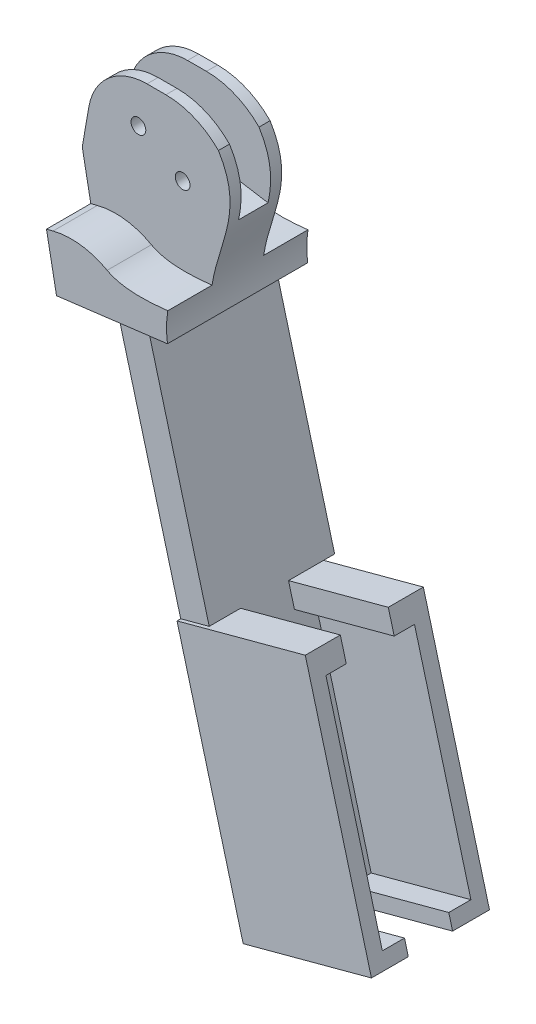
SolidWorks part; units mm, degrees
ref_plane "Спереди" through (0, 0, 0) normal (0, 0, 1) x (1, 0, 0)
ref_plane "Сверху" through (0, 0, 0) normal (0, 1, 0) x (1, 0, 0)
ref_plane "Справа" through (0, 0, 0) normal (1, 0, 0) x (0, 0, -1)
sketch "Sketch5" plane through (0, 0, 0) normal (0, 0, 1) x (1, 0, 0)
  line L0 (1.7523, 0.4742) -> (37.3029, 86.8114) construction
  line L1 (-1.0106, -0.6044) -> (29.6618, 87.5839) construction
  line L2 (0, 0) -> (17.8901, 43.1295)
  line L3 (0, 0) -> (114.3643, 0) construction
  line L4 (23.8823, 39.6684) -> (24.5035, 51.2503)
  line B0 (17.4507, 115.16) -> (29.9551, 112.6983)
  spline B1 degree 3 poles (29.9551, 112.6983) (28.321, 116.0983) (27.9284, 121.1676) (30.1713, 134.4746) (29.8473, 132.0116) (30.6222, 139.9349) (27.0176, 140.9027) knots 0 0 0 0 0.297085 0.369784 0.687298 1 1 1 1
  spline B2 degree 2 poles (27.0176, 140.9027) (20.5603, 128.6427) (17.4507, 115.16) knots 0 0 0 1 1 1
  spline B3 degree 2 poles (27.0176, 140.9027) (26.5004, 134.6878) (22.2537, 130.5645) knots 0 0 0 1 1 1
  line B4 (17.1977, 114.3508) -> (29.842, 112.2111)
  line B5 (28.7001, 84.8969) -> (10.3668, 87.513)
  spline B6 degree 1 poles (17.1977, 114.3508) (10.3668, 87.513) knots 0 0 1 1
  spline B7 degree 2 poles (29.842, 112.2111) (22.5534, 98.8452) (28.7001, 84.8969) knots 0 0 0 1 1 1
  line B8 (10.1904, 87.4159) -> (28.2572, 84.4958)
  line B9 (32.8909, 45.7292) -> (10.0695, 42.8593)
  spline B10 degree 2 poles (10.1904, 87.4159) (10.0234, 65.1379) (10.0695, 42.8593) knots 0 0 0 1 1 1
  spline B11 degree 2 poles (28.2572, 84.4958) (20.6417, 64.1094) (32.8909, 45.7292) knots 0 0 0 1 1 1
  line B12 (10.2797, 36.8758) -> (3.9253, -13.9853)
  line B13 (3.9253, -13.9853) -> (33.9594, -31.0804)
  line B14 (33.9594, -31.0804) -> (45.9193, -27.7969)
  line B15 (45.9193, -27.7969) -> (58.2918, -13.9853)
  line B16 (58.2918, -13.9853) -> (69.0331, -4.9875)
  line B17 (69.0331, -4.9875) -> (82.514, 2.0236)
  line B18 (82.514, 2.0236) -> (89.2736, 3.8794)
  line B19 (89.2736, 3.8794) -> (92.4846, 9.5208)
  line B20 (92.4846, 9.5208) -> (96.8914, 17.263)
  line B21 (96.8914, 17.263) -> (101.4978, 21.1217)
  line B22 (101.4978, 21.1217) -> (103.9241, 23.1541)
  line B23 (104.261, 27.4157) -> (104.5375, 25.5318)
  line B24 (84.192, 21.2056) -> (87.7484, 22.7822)
  line B25 (87.7484, 22.7822) -> (92.912, 27.4956)
  line B26 (71.6086, 15.6268) -> (84.192, 21.2056)
  line B27 (92.912, 27.4956) -> (95.357, 29.7274)
  line B28 (95.357, 29.7274) -> (96.8049, 29.9399)
  line B29 (71.6086, 15.6268) -> (53.4239, 15.2713)
  line B30 (48.0904, 17.5622) -> (39.9394, 26.4919)
  line B31 (39.9394, 26.4919) -> (33.9594, 37.99)
  line B32 (33.9594, 37.99) -> (10.2797, 36.8758)
  line B33 (96.8049, 29.9399) -> (99.4078, 30.2175)
  line B34 (99.4078, 30.2175) -> (102.2786, 29.261)
  line B35 (102.2786, 29.261) -> (104.261, 27.4157)
  line B36 (104.5375, 25.5318) -> (103.9241, 23.1541)
  arc B37 (53.4239, 15.2713) -> (48.0904, 17.5622) centre (53.2864, 22.3051) cw
  spline B38 degree 3 poles (104.261, 27.4157) (103.5289, 27.0494) (99.8378, 26.2685) (94.8982, 17.2338) (98.6516, 18.7375) knots 0 0 0 0 0.441207 1 1 1 1
  line B39 (27.7375, 116.5129) -> (14.1959, 87.8955)
  line B40 (27.7375, 116.5129) -> (25.9485, 114.8372)
  line B41 (25.9485, 114.8372) -> (27.5763, 114.067)
  line B42 (27.7375, 116.5129) -> (27.5763, 114.067)
  line B43 (26.1527, 88.0864) -> (17.8901, 43.1295)
  line B44 (19.3622, 85.005) -> (23.8823, 39.6684)
  line B45 (19.3622, 85.005) -> (17.7584, 73.9508)
  line B46 (17.7584, 73.9508) -> (23.117, 74.485)
  line B47 (23.117, 74.485) -> (19.3622, 85.005)
  line B48 (26.1527, 88.0864) -> (23.7481, 82.7635)
  line B49 (23.7481, 82.7635) -> (25.1278, 82.5099)
  line B50 (25.1278, 82.5099) -> (26.5087, 82.2561)
  line B51 (26.5087, 82.2561) -> (26.1527, 88.0864)
  line B52 (26.1527, 88.0864) -> (19.3622, 85.005)
  line B53 (19.3622, 85.005) -> (22.3683, 87.7853)
  line B54 (22.3683, 87.7853) -> (22.9012, 86.6109)
  line B55 (22.9012, 86.6109) -> (23.4998, 85.2917)
  line B56 (23.4998, 85.2917) -> (19.3622, 85.005)
  dimension "D1" = 93.37
  dimension "D2" = 93.37
  dimension "D4" = 67.471
  dimension "D5" = 8.764
sketch_block_instance "Block1-1"
sketch_block "Block1"
sketch_block_instance "Block2-1"
sketch_block "Block2"
sketch_block_instance "Block3-1"
sketch_block "Block3"
sketch_block_instance "Block18-1"
sketch_block "Block18"
sketch_block_instance "Block44-1"
sketch_block "Block44"
sketch_block_instance "Block46-1"
sketch_block "Block46"
sketch_block_instance "Block47-1"
sketch_block "Block47"
sketch_block_instance "Block48-1"
sketch_block "Block48"
sketch_block_instance "Block50-1"
sketch_block "Block50"
sketch "Sketch10" plane through (0, 0, 0) normal (0, 0, 1) x (1, 0, 0)
  line L0 (27.0489, 48.6569) -> (33.9594, 37.99)
  line L3 (33.9594, 37.99) -> (36.9938, 26.6828)
  line L21 (10.2797, 36.8758) -> (12.7888, 23.6588)
  line L22 (12.7888, 23.6588) -> (36.9938, 26.6828)
  line L23 (10.2797, 36.8758) -> (12.3218, 48.6569)
  line L24 (12.3218, 48.6569) -> (27.0489, 48.6569)
  circle A0 centre (17.8901, 43.1295) radius 1
  circle A1 centre (23.8823, 39.6684) radius 1
  dimension "D1" = 2
extrude "Boss-Extrude5" add sketch "Sketch10" along normal mid plane 15
sketch "Sketch11" plane through (0, 0, 7.5) normal (0, 0, 1) x (1, 0, 0)
  line L0 (17.8254, 32.4239) -> (9.1239, 30.2079)
  line L1 (37.7529, 30.846) -> (34.6935, 60.2717)
  line L2 (34.6935, 60.2717) -> (6.5943, 53.1599)
  line L3 (6.5943, 53.1599) -> (9.1239, 30.2079)
  line L4 (37.7529, 30.846) -> (30.6791, 30.1551) construction
  line L5 (30.6791, 30.1551) -> (19.269, 26.7342) construction
  line L6 (19.269, 26.7342) -> (17.8254, 32.4239) construction
  line L7 (12.3218, 48.6569) -> (10.2797, 36.8758) construction
  spline S1 degree 3 poles (37.7529, 30.846) (30.6791, 30.1551) (19.269, 26.7342) (17.8254, 32.4239) knots 0 0 0 0 1 1 1 1
extrude "Cut-Extrude1" cut sketch "Sketch11" against normal blind 4
fillet "Fillet1" radius 10 1 edges at (27.0489, 48.6569, -2)
extrude "Cut-Extrude6" cut sketch "Sketch11<2>" against normal blind 10 from offset 11 offset against normal yes
sketch "Sketch11<2>" plane through (0, 0, 7.5) normal (0, 0, 1) x (1, 0, 0) same geometry as "Sketch11"
sketch "Sketch16" plane through (0, 0, 0) normal (0, 0, 1) x (1, 0, 0)
  line L1 (10.0743, 54.3608) -> (34.4186, 54.3608)
  line L2 (10.0743, 54.3608) -> (10.0743, 40.6451)
  line L3 (10.0743, 40.6451) -> (34.4186, 36.6644)
  line L4 (34.4186, 54.3608) -> (34.4186, 36.6644)
extrude "Cut-Extrude7" cut sketch "Sketch16" against normal mid plane 4
sketch "Sketch26" plane through (41.1882, 11.0532, 0) normal (0.9658, 0.2592, 0) x (0, 0, -1)
  line L12 (2, 27.8898) -> (2, 26.5356)
  line L13 (2, 26.5356) -> (-2, 26.5356)
  line L14 (-2, 26.5356) -> (-2, 27.8898)
  line L15 (-2, 27.8898) -> (-3.5, 27.8898)
  line L16 (-3.5, 27.8898) -> (-3.5, 20.2671)
  line L17 (-3.5, 20.2671) -> (-7.5, 20.2671)
  line L18 (-7.5, 20.2671) -> (-7.5, 16.1826)
  line L19 (-7.5, 16.1826) -> (7.5, 16.1826)
  line L20 (7.5, 16.1826) -> (7.5, 20.2671)
  line L21 (7.5, 20.2671) -> (3.5, 20.2671)
  line L22 (3.5, 20.2671) -> (3.5, 27.8898)
  line L23 (3.5, 27.8898) -> (2, 27.8898)
  line L24 (2, 27.8898) -> (2, 26.5356)
  line L25 (2, 26.5356) -> (-2, 26.5356)
  line L26 (-2, 26.5356) -> (-2, 27.8898)
  line L27 (-2, 27.8898) -> (-3.5, 27.8898)
  line L28 (-3.5, 27.8898) -> (-3.5, 20.2671)
  line L29 (-3.5, 20.2671) -> (-7.5, 20.2671)
  line L30 (-7.5, 20.2671) -> (-7.5, 16.1826)
  line L31 (-7.5, 16.1826) -> (7.5, 16.1826)
  line L32 (7.5, 16.1826) -> (7.5, 20.2671)
  line L33 (7.5, 20.2671) -> (3.5, 20.2671)
  line L34 (3.5, 20.2671) -> (3.5, 27.8898)
  line L35 (3.5, 27.8898) -> (2, 27.8898)
  dimension "D1" = 0
extrude "Boss-Extrude11" add sketch "Sketch26" along normal blind 9
sketch "Sketch30" plane through (-4.1944, 15.6296, 0) normal (0.2592, -0.9658, 0) x (0.9658, 0.2592, 0)
  line L0 (51.6455, 7.5) -> (42.6455, 7.5) construction
  line L1 (51.6455, 7.5) -> (26.6455, 7.5)
  line L2 (51.6455, 7.5) -> (51.6455, -7.5)
  line L3 (51.6455, -7.5) -> (26.6455, -7.5)
  line L4 (26.6455, 7.5) -> (26.6455, -7.5)
  line L5 (18.4838, -7.5) -> (42.6455, -7.5) construction
  line L6 (51.6455, 7.5) -> (51.6455, -7.5) construction
  line L7 (51.6455, -7.5) -> (42.6455, -7.5) construction
  line L9 (28.6455, 7.5) -> (26.6455, 7.5)
  line L10 (28.6455, 7.5) -> (28.6455, -7.5)
  line L11 (28.6455, -7.5) -> (26.6455, -7.5)
  line L12 (26.6455, 7.5) -> (26.6455, -7.5)
  line L13 (26.6455, 7.5) -> (24.6455, 7.5)
  line L14 (26.6455, 7.5) -> (26.6455, -7.5)
  line L15 (26.6455, -7.5) -> (24.6455, -7.5)
  line L16 (24.6455, 7.5) -> (24.6455, -7.5)
  dimension "D1" = 25
  dimension "D2" = 2
  dimension "D3" = 2
extrude "Boss-Extrude13" add sketch "Sketch30" along normal blind 64 and the other way blind 3 contours L10 L1 L4 L3 | L13 L16 L15 L4 region at (22.5064, 22.795, 0) region at (20.5748, 22.2766, 0)
sketch "Sketch31" plane through (27.6666, 7.4246, 0) normal (0.9658, 0.2592, 0) x (0, 0, -1)
  line L0 (-7.5, 16.1826) -> (7.5, 16.1826) construction
  line L1 (-6, -17.8174) -> (-3.25, -17.8174)
  line L2 (-6, -17.8174) -> (-6, -47.3174)
  line L3 (-6, -47.3174) -> (-3, -47.3174)
  line L4 (6, -17.8174) -> (6, -47.3174)
  line L5 (0, 0) -> (0, -17.1237) construction
  line L6 (0, -17.1237) -> (0, -50.3713) construction
  line L7 (-6, -17.8174) -> (-8, -17.8174)
  line L8 (-6, -17.8174) -> (-6, -47.3174)
  line L9 (-6, -47.3174) -> (-8, -47.3174)
  line L10 (-8, -17.8174) -> (-8, -47.3174)
  line L11 (6, -17.8174) -> (8, -17.8174)
  line L12 (6, -17.8174) -> (6, -47.3174)
  line L13 (6, -47.3174) -> (8, -47.3174)
  line L14 (8, -17.8174) -> (8, -47.3174)
  line L15 (-8, -17.8174) -> (-3.25, -17.8174)
  line L16 (-8, -17.8174) -> (-8, -14.7312)
  line L17 (-8, -14.7312) -> (-3.25, -14.7312)
  line L18 (8, -17.8174) -> (8, -14.7312)
  line L19 (8, -47.3174) -> (3, -47.3174)
  line L20 (8, -47.3174) -> (8, -49.3174)
  line L21 (8, -49.3174) -> (3, -49.3174)
  line L22 (-8, -47.3174) -> (-8, -49.3174)
  line L23 (-3.25, -17.8174) -> (-3.25, -14.7312)
  line L24 (3.25, -17.8174) -> (3.25, -14.7312)
  line L25 (3.25, -14.7312) -> (8, -14.7312)
  line L26 (3.25, -17.8174) -> (6, -17.8174)
  line L27 (3.25, -17.8174) -> (8, -17.8174)
  line L28 (-3, -47.3174) -> (-3, -49.3174)
  line L29 (3, -47.3174) -> (3, -49.3174)
  line L30 (-3, -49.3174) -> (-8, -49.3174)
  line L31 (3, -47.3174) -> (6, -47.3174)
  line L32 (-3, -47.3174) -> (-8, -47.3174)
  line L33 (-3.25, -17.1237) -> (3.25, -17.1237) construction
  line L34 (-3, -50.3713) -> (3, -50.3713) construction
  point P4 (0, -17.1237)
  point P20 (0, -17.1237)
  point P21 (5.5, -49.3174)
  point P29 (0, -17.1237)
  point P34 (0, -50.3713)
  point P35 (5.5, -47.3174)
  line M4 (7.5, -47.8174) -> (7.5, 18.1255)
  line M6 (-7.5, 18.1255) -> (-7.5, -47.8174)
  line M7 (-7.5, -47.8174) -> (7.5, -47.8174)
  dimension "D1" = 12
  dimension "D2" = 34
  dimension "D3" = 29.5
  dimension "D4" = 6
  dimension "D5" = 2
  dimension "D6" = 2
  dimension "D7" = 2
  dimension "D8" = 6.5
extrude "Boss-Extrude14" add sketch "Sketch31" along normal blind 14 and the other way blind 4 contours L9 L2 L7 M6 | L7 L10 L9 M6 | L4 L13 L11 M4 | L14 L11 L13 M4 | L28 L3 L9 M6 M7 | L29 L21 L20 L13 M7 M4 | L19 L29 L13 M7 M4 | L30 L28 L9 L22 M7 M6 | L1 L23 L17 L7 M6 | L24 L26 L11 L25 M4 | L25 L11 L18 M4 | L17 L16 L7 M6 region at (31.8847, -8.2935, 5.375) region at (39.9955, -38.5173, -5.25) region at (40.2464, -39.4519, -5.5726) region at (36.1077, -24.0299, 6.75) region at (39.9955, -38.5173, 5.25) region at (36.1077, -24.0299, 7.75) region at (31.8847, -8.2935, 7.75) region at (40.2464, -39.4519, 5.5726) region at (36.1077, -24.0299, -6.75) region at (36.1077, -24.0299, -7.75) region at (31.8847, -8.2935, -5.375) region at (31.8847, -8.2935, -7.75)
sketch "Sketch32" plane through (49.8806, 13.3859, 0) normal (0.9658, 0.2592, 0) x (0, 0, -1)
  line L12 (3.5, 27.8898) -> (2, 27.8898)
  line L13 (2, 27.8898) -> (2, 26.5356)
  line L14 (2, 26.5356) -> (-2, 26.5356)
  line L15 (-2, 26.5356) -> (-2, 27.8898)
  line L16 (-2, 27.8898) -> (-3.5, 27.8898)
  line L17 (-3.5, 27.8898) -> (-3.5, 20.2671)
  line L18 (-3.5, 20.2671) -> (-7.5, 20.2671)
  line L19 (-7.5, 20.2671) -> (-7.5, 16.1826)
  line L20 (-7.5, 16.1826) -> (7.5, 16.1826)
  line L21 (7.5, 16.1826) -> (7.5, 20.2671)
  line L22 (7.5, 20.2671) -> (3.5, 20.2671)
  line L23 (3.5, 20.2671) -> (3.5, 27.8898)
  line L24 (3.5, 27.8898) -> (2, 27.8898)
  line L25 (2, 27.8898) -> (2, 26.5356)
  line L26 (2, 26.5356) -> (-2, 26.5356)
  line L27 (-2, 26.5356) -> (-2, 27.8898)
  line L28 (-2, 27.8898) -> (-3.5, 27.8898)
  line L29 (-3.5, 27.8898) -> (-3.5, 20.2671)
  line L30 (-3.5, 20.2671) -> (-7.5, 20.2671)
  line L31 (-7.5, 20.2671) -> (-7.5, 16.1826)
  line L32 (-7.5, 16.1826) -> (7.5, 16.1826)
  line L33 (7.5, 16.1826) -> (7.5, 20.2671)
  line L34 (7.5, 20.2671) -> (3.5, 20.2671)
  line L35 (3.5, 20.2671) -> (3.5, 27.8898)
  dimension "D1" = 0
extrude "Cut-Extrude9" cut sketch "Sketch32" against normal blind 9
fillet "Fillet2" radius 8 2 edges at (12.3218, 48.6569, 2.75) (12.3218, 48.6569, -2.75)
fillet "Fillet3" radius 10 2 edges at (17.8254, 32.4239, 5.5) (17.8254, 32.4239, -5.5)
sketch "Sketch33" plane through (0, 0, -7.5) normal (0, 0, -1) x (-1, 0, 0)
  line L8 (-11.4338, 30.7962) -> (-12.3264, 31.0235)
  line L9 (-35.9352, 30.6278) -> (-36.9938, 26.6828)
  line L10 (-36.9938, 26.6828) -> (-22.9687, 24.9306)
  line L11 (-22.9687, 24.9306) -> (-31.4847, -6.8032)
  line L12 (-31.4847, -6.8032) -> (-27.6214, -7.8399)
  line L13 (-27.6214, -7.8399) -> (-18.9615, 24.43)
  line L14 (-18.9615, 24.43) -> (-12.7888, 23.6588)
  line L15 (-12.7888, 23.6588) -> (-11.4338, 30.7962)
  line L16 (-11.4338, 30.7962) -> (-12.3264, 31.0235)
  line L17 (-35.9352, 30.6278) -> (-36.9938, 26.6828)
  line L18 (-36.9938, 26.6828) -> (-22.9687, 24.9306)
  line L19 (-18.9615, 24.43) -> (-12.7888, 23.6588)
  line L23 (-12.7888, 23.6588) -> (-11.4338, 30.7962)
  arc A1 (-12.3264, 31.0235) -> (-19.6523, 30.0735) centre (-14.7943, 21.3328) ccw
  arc A2 (-12.3264, 31.0235) -> (-19.6523, 30.0735) centre (-14.7943, 21.3328) ccw
  spline S1 degree 3 poles (-2248.4396, 2036.9091) (2398.2094, -1976.4445) (-2488.5969, 2006.9634) (2269.009, -1889.1266) knots -4.784798 -4.784798 -4.784798 -4.784798 6.242237 6.242237 6.242237 6.242237 only from (-19.6523, 30.0735) to (-35.9352, 30.6278)
  spline S2 degree 3 poles (-19.6523, 30.0735) (-23.0942, 28.1606) (-30.3498, 29.8586) (-35.9352, 30.6278) knots 0.191604 0.191604 0.191604 0.191604 0.918086 0.918086 0.918086 0.918086
  line M11 (-11.4338, 30.7962) -> (-12.3264, 31.0235)
  arc M12 (-12.3264, 31.0235) -> (-19.6523, 30.0735) centre (-14.7943, 21.3328) ccw
  spline M13 degree 3 poles (-37.7529, 30.846) (-30.6791, 30.1551) (-19.269, 26.7342) (-17.8254, 32.4239) knots 0 0 0 0 1 1 1 1 only from (-19.6523, 30.0735) to (-35.9352, 30.6278)
  line M14 (-35.9352, 30.6278) -> (-36.9938, 26.6828)
  line M15 (-36.9938, 26.6828) -> (-22.9687, 24.9306)
  line M16 (-22.9687, 24.9306) -> (-31.4847, -6.8032)
  line M17 (-31.4847, -6.8032) -> (-27.6214, -7.8399)
  line M18 (-27.6214, -7.8399) -> (-18.9615, 24.43)
  line M19 (-18.9615, 24.43) -> (-12.7888, 23.6588)
  line M20 (-12.7888, 23.6588) -> (-11.4338, 30.7962)
  dimension "D1" = 0
extrude "Boss-Extrude15" add sketch "Sketch33" along normal blind 2 contours M20 M11 M12 M13 M14 M15 M16 M17 M18 M19 region at (23.9735, 17.7801, -7.5)
sketch "Sketch34" plane through (0, 0, 7.5) normal (0, 0, 1) x (1, 0, 0)
  line L8 (12.3264, 31.0235) -> (11.4338, 30.7962)
  line L9 (11.4338, 30.7962) -> (12.7888, 23.6588)
  line L10 (12.7888, 23.6588) -> (18.9615, 24.43)
  line L11 (18.9615, 24.43) -> (27.6214, -7.8399)
  line L12 (27.6214, -7.8399) -> (31.4847, -6.8032)
  line L13 (31.4847, -6.8032) -> (22.9687, 24.9306)
  line L14 (22.9687, 24.9306) -> (36.9938, 26.6828)
  line L15 (36.9938, 26.6828) -> (35.9352, 30.6278)
  line L16 (12.3264, 31.0235) -> (11.4338, 30.7962)
  line L17 (11.4338, 30.7962) -> (12.7888, 23.6588)
  line L18 (12.7888, 23.6588) -> (22.9687, 24.9306)
  line L19 (22.9687, 24.9306) -> (36.9938, 26.6828)
  line L23 (36.9938, 26.6828) -> (35.9352, 30.6278)
  arc A1 (19.6523, 30.0735) -> (12.3264, 31.0235) centre (14.7943, 21.3328) ccw
  arc A2 (19.6523, 30.0735) -> (12.3264, 31.0235) centre (14.7943, 21.3328) ccw
  spline S1 degree 3 poles (-2269.0749, -1889.1805) (2488.6505, 2007.0071) (-2398.2482, -1976.4772) (2248.4643, 2036.9304) knots -5.132598 -5.132598 -5.132598 -5.132598 5.894507 5.894507 5.894507 5.894507 only from (35.9352, 30.6278) to (19.6523, 30.0735)
  spline S2 degree 3 poles (35.9352, 30.6278) (30.3498, 29.8586) (23.0942, 28.1606) (19.6523, 30.0735) knots 0.191604 0.191604 0.191604 0.191604 0.918086 0.918086 0.918086 0.918086
  dimension "D1" = 0
extrude "Boss-Extrude16" add sketch "Sketch34" along normal blind 2
sketch "Sketch36" plane through (0, 0, 9.5) normal (0, 0, 1) x (1, 0, 0)
  line L0 (28.7352, 45.6757) -> (36.2045, 33.6087) construction
  line L1 (36.2045, 33.6087) -> (15.1025, 27.6168) construction
  line L2 (15.1025, 27.6168) -> (34.9887, 13.2015) construction
  line L3 (34.9887, 13.2015) -> (40.6333, 13.2015) construction
  line L4 (28.7352, 45.6757) -> (43.1516, 50.0214)
  line L5 (43.1516, 50.0214) -> (48.7093, 19.4539)
  line L6 (48.7093, 19.4539) -> (40.6333, 13.2015)
  arc A0 (30.0049, 44.0941) -> (21.6122, 48.6569) centre (21.6122, 38.6569) ccw construction
  spline S0 degree 4 poles (28.7352, 45.6757) (36.2045, 33.6087) (15.1025, 27.6168) (34.9887, 13.2015) (40.6333, 13.2015) knots 0 0 0 0 0 1 1 1 1 1
extrude "Cut-Extrude10" cut sketch "Sketch36" against normal blind 28
